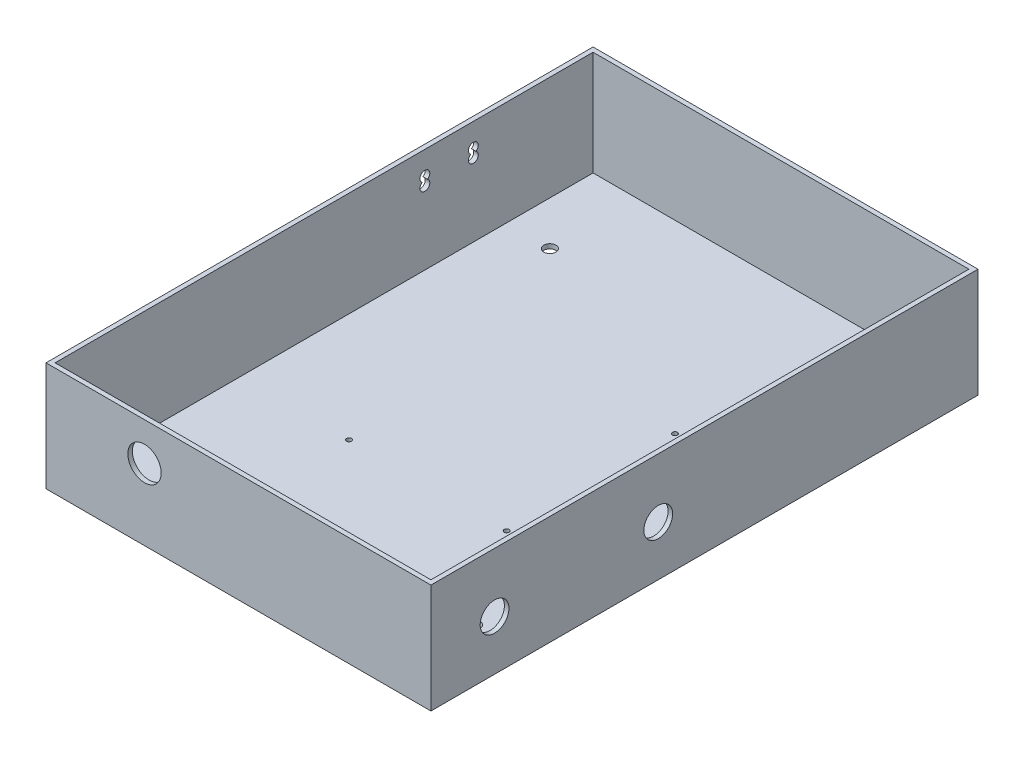
SolidWorks part; units mm, degrees
ref_plane "Front Plane" through (0, 0, 0) normal (0, 0, 1) x (1, 0, 0)
ref_plane "Top Plane" through (0, 0, 0) normal (0, 1, 0) x (1, 0, 0)
ref_plane "Right Plane" through (0, 0, 0) normal (1, 0, 0) x (0, 0, -1)
sketch "Sketch1" plane through (0, 0, 0) normal (0, 1, 0) x (1, 0, 0)
  line L0 (-3, 3) -> (251, 3)
  line L1 (0, 0) -> (248, 0)
  line L2 (0, 0) -> (0, -355)
  line L3 (0, -355) -> (248, -355)
  line L4 (248, 0) -> (248, -355)
  line L5 (251, 3) -> (251, -358)
  line L6 (-3, -358) -> (251, -358)
  line L7 (-3, 3) -> (-3, -358)
  dimension "D1" = 248
  dimension "D2" = 355
  dimension "D3" = 3
extrude "Boss-Extrude1" add sketch "Sketch1" along normal blind 3 contours L4 L1 L2 L3 | L0 L7 L6 L5 L1 L4 L3 L2 region at (124, 0, -2.5586) region at (124, 0, 177.5)
extrude "Boss-Extrude2" add sketch "Sketch1<3>" along normal blind 69 from surface starting at face at (124, 3, 177.5)
sketch "Sketch1<3>" plane through (0, 0, 0) normal (0, 1, 0) x (1, 0, 0) same geometry as "Sketch1"
sketch "Sketch2" plane through (251, 0, 0) normal (1, 0, 0) x (0, 0, -1)
  line L0 (-316, 72) -> (-316, 33) construction
  line L1 (3, 72) -> (-358, 72) construction
  line L2 (-316, 33) -> (-358, 33) construction
  line L3 (-358, 72) -> (-358, 0) construction
  line L4 (-316, 33) -> (-208, 33) construction
  circle A0 centre (-316, 33) radius 9.5
  circle A1 centre (-208, 33) radius 9.5
  dimension "D1" = 19
  dimension "D2" = 39
  dimension "D3" = 42
  dimension "D4" = 108
extrude "Cut-Extrude1" cut sketch "Sketch2" against normal up to surface (3 mm away) up to face at (248, 37.5, 177.5)
sketch "Sketch3" plane through (0, 0, 358) normal (0, 0, 1) x (1, 0, 0)
  line L0 (-3, 47) -> (62, 47) construction
  line L1 (-3, 72) -> (-3, 0) construction
  line L2 (62, 47) -> (62, 72) construction
  line L3 (251, 72) -> (-3, 72) construction
  circle A0 centre (62, 47) radius 11
  dimension "D1" = 22
  dimension "D2" = 25
  dimension "D3" = 65
extrude "Cut-Extrude2" cut sketch "Sketch3" against normal up to surface (3 mm away) up to face at (124, 37.5, 355)
sketch "Sketch4" plane through (-3, 0, 0) normal (-1, 0, 0) x (0, 0, 1)
  line L0 (79, 51.25) -> (79, 56.75) construction
  line L1 (111, 51.25) -> (111, 56.75) construction
  line L2 (111, 54) -> (79, 54) construction
  line L3 (79, 54) -> (-3, 54) construction
  line L4 (-3, 72) -> (-3, 0) construction
  line L5 (95, 54) -> (95, 72) construction
  line L6 (358, 72) -> (-3, 72) construction
  circle A0 centre (79, 56.75) radius 3.25
  circle A1 centre (79, 51.25) radius 3.25
  circle A2 centre (111, 56.75) radius 3.25
  circle A3 centre (111, 51.25) radius 3.25
  dimension "D1" = 6.5
  dimension "D2" = 5.5
  dimension "D3" = 82
  dimension "D4" = 18
  dimension "D5" = 32
extrude "Cut-Extrude3" cut sketch "Sketch4" against normal up to surface (3 mm away) contours A1 A0 | A0 A1 | A0 A1 | A2 A3 | A2 A3 | A3 A2 region at (-3, 56.9594, 79) region at (-3, 54, 79) region at (-3, 51.0406, 79) region at (-3, 56.9594, 111) region at (-3, 54, 111) region at (-3, 51.0406, 111) up to face at (0, 37.5, 177.5)
sketch "Sketch5" plane through (0, 3, 0) normal (0, 1, 0) x (1, 0, 0)
  line L0 (124, 3) -> (124, -358) construction
  line L1 (-3, 3) -> (251, 3) construction
  line L2 (251, -358) -> (-3, -358) construction
  line L3 (-3, -177.5) -> (251, -177.5) construction
  line L4 (-3, -358) -> (-3, 3) construction
  line L5 (251, 3) -> (251, -358) construction
  line L6 (219, -297.5) -> (29, -297.5) construction
  line L7 (29, -297.5) -> (29, -57.5) construction
  line L8 (29, -57.5) -> (219, -57.5) construction
  line L9 (219, -57.5) -> (219, -297.5) construction
  line L10 (176, -233) -> (251, -233) construction
  line L11 (176, -233) -> (176, -358) construction
  line L12 (176, -233) -> (176, -122) construction
  line L13 (176, -233) -> (72, -233) construction
  circle A0 centre (29, -297.5) radius 7
  circle A1 centre (219, -297.5) radius 7
  circle A2 centre (29, -57.5) radius 7
  circle A3 centre (219, -57.5) radius 7
  circle A4 centre (176, -233) radius 5
  circle A5 centre (176, -122) radius 5
  circle A6 centre (72, -233) radius 5
  circle A7 centre (29, -57.5) radius 4
  circle A8 centre (219, -57.5) radius 4
  circle A9 centre (29, -297.5) radius 4
  circle A10 centre (219, -297.5) radius 4
  point P21 (124, -57.5)
  point P22 (219, -177.5)
  point P23 (176, -177.5)
  point P29 (124, -233)
  dimension "D1" = 14
  dimension "D4" = 10
  dimension "D7" = 8
  dimension "D2" = 190
  dimension "D3" = 240
  dimension "D5" = 75
  dimension "D6" = 125
extrude "Cut-Extrude4" cut sketch "Sketch5" against normal up to surface (3 mm away) contours A9 | A10 | A7 | A8 region at (29, 3, 57.5) region at (219, 3, 57.5) region at (29, 3, 297.5) region at (219, 3, 297.5) up to face at (124, 0, 177.5)
hole_wizard "M4x0.7 Tapped Hole1" positions "Sketch11" profile "Sketch12" tap size "M4x0.7" standard "ANSI Metric" end condition through all
sketch "Sketch11" plane through (0, 3, 0) normal (0, 1, 0) x (1, 0, 0)
  line L0 (124, -358) -> (124, 3) construction
  line L1 (251, -358) -> (-3, -358) construction
  line L2 (-3, 3) -> (251, 3) construction
  line L4 (-3, -177.5) -> (251, -177.5) construction
  line L5 (-3, -358) -> (-3, 3) construction
  line L6 (251, 3) -> (251, -358) construction
  line L8 (176, -233) -> (176, -122) construction
  line L10 (72, -233) -> (176, -233) construction
  point P0 (72, -233)
  point P2 (176, -233)
  point P4 (176, -122)
  point P30 (124, -233)
  point P31 (176, -177.5)
  dimension "D1" = 104
  dimension "D2" = 111
sketch "Sketch12" plane through (72, 3, 233) normal (1, 0, 0) x (0, 0, 1)
  line L0 (0, 0) -> (0, 3)
  line L1 (0, 3) -> (1.65, 3)
  line L2 (1.65, 3) -> (1.65, 0)
  line L5 (1.65, 0) -> (0, 0)
  line L11 (0, -6.35) -> (0, 107.95) construction
  dimension "Thru Tap Drill Dia." = 3.3
  dimension "Thru Tap Drill Depth" = 3
cosmetic thread "Hole Thread1" parameters "D2"=4
cosmetic thread "Hole Thread2" parameters "D2"=4
cosmetic thread "Hole Thread3" parameters "D2"=4
